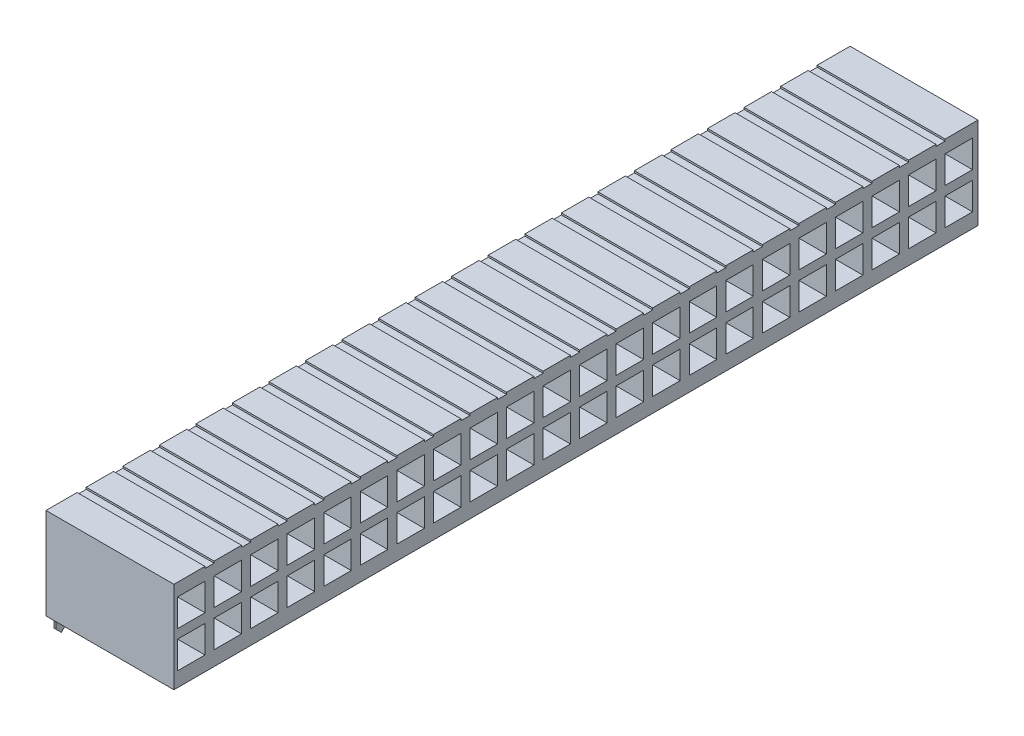
SolidWorks part; units mm, degrees
ref_plane "Alzado" through (0, 0, 0) normal (0, 0, 1) x (1, 0, 0)
ref_plane "Planta" through (0, 0, 0) normal (0, 1, 0) x (1, 0, 0)
ref_plane "Vista lateral" through (0, 0, 0) normal (1, 0, 0) x (0, 0, -1)
sketch "Croquis1" plane through (0, 0, 0) normal (1, 0, 0) x (0, 0, -1)
  line L1 (-22, 2.5) -> (22, 2.5)
  line L2 (-22, 2.5) -> (-22, -2.5)
  line L3 (-22, -2.5) -> (22, -2.5)
  line L4 (22, 2.5) -> (22, -2.5)
  line L5 (-22, 2.5) -> (22, -2.5) construction
  line L6 (-22, -2.5) -> (22, 2.5) construction
  point P0 (0, 0)
  dimension "D1" = 44
  dimension "D2" = 5
extrude "Extruir1" add sketch "Croquis1" along normal mid plane 7
sketch "Croquis2" plane through (3.5, 0, 0) normal (1, 0, 0) x (0, 0, -1)
  line L0 (22, 2.5) -> (-22, 2.5) construction
  line L1 (-21.8, 1.8) -> (-20.3, 1.8)
  line L2 (-21.8, 1.8) -> (-21.8, 0.3)
  line L3 (-21.8, 0.3) -> (-20.3, 0.3)
  line L4 (-20.3, 1.8) -> (-20.3, 0.3)
  line L5 (-21.8, 1.8) -> (-20.3, 0.3) construction
  line L6 (-21.8, 0.3) -> (-20.3, 1.8) construction
  line L7 (-22, 2.5) -> (-22, -2.5) construction
  point P0 (-21.05, 1.05)
  dimension "D1" = 1.5
  dimension "D2" = 1.5
  dimension "D3" = 0.7
  dimension "D4" = 0.2
extrude "Extruir2" cut sketch "Croquis2" against normal through all
pattern_linear "MatrizL1" count 22 spacing 2 along (0, 0, -1) count 2 spacing 2 along (0, -1, 0) of "Extruir2"
sketch "Croquis3" plane through (0, 0.3, 0) normal (0, 1, 0) x (1, 0, 0)
  line L2 (-3.6, -21.8) -> (0.1785, -21.8)
  line L3 (-3.6, -20.3) -> (0.1785, -20.3)
  line L4 (0.1785, -20.3) -> (0.1785, -21.8)
  line L5 (-3.5, 22) -> (-3.5, -22) construction
  line L6 (-3.6, -20.3) -> (-3.6, -21.8)
  line L7 (3.5, -21.8) -> (3.5, -20.3) construction
  line L8 (-3.5, -20.3) -> (3.5, -20.3) construction
  dimension "D1" = 0.1
  dimension "D2" = 3.3215
  dimension "D3" = 1.5
extrude "Extruir3" add sketch "Croquis3" along normal blind 0.1
sketch "Croquis5" plane through (-3.6, 0, 0) normal (-1, 0, 0) x (0, 0, 1)
  line L0 (20.3, 0.4) -> (20.3, -1.7)
  line L1 (22, -2.5) -> (-22, -2.5) construction
  line L2 (20.3, 0.4) -> (21.8, 0.4)
  line L3 (21.8, 0.4) -> (21.8, -1.7)
  line L4 (21.8, -1.7) -> (20.3, -1.7) construction
  line L5 (20.3, -1.7) -> (20.76, -2.5)
  line L6 (21.8, -0.2) -> (21.8, -1.7) construction
  line L7 (21.8, -1.7) -> (21.3581, -2.5)
  line L8 (21.3581, -2.5) -> (21.3581, -3.5031)
  line L9 (21.3581, -3.5031) -> (21.0591, -3.8022)
  line L10 (21.0591, -3.8022) -> (20.76, -3.5031)
  line L11 (20.76, -3.5031) -> (20.76, -2.5)
  line L12 (20.3, 0.3) -> (21.8, 0.3) construction
  dimension "D1" = 0.4419
  dimension "D2" = 0.7409
  dimension "D3" = 0.1
  dimension "D4" = 1.5
  dimension "D5" = 3.8031
extrude "Extruir9" add sketch "Croquis5" along normal blind 0.1
sketch "Croquis8" plane through (-3.6, 0, 0) normal (1, 0, 0) x (0, 0, -1)
  line L0 (-20.3, 0.3) -> (-20.3, -1.7) construction
  line L1 (-21.8, -1.7) -> (-20.3, -1.7)
  line L2 (-21.8, -1.7) -> (-21.8, -1.6)
  line L3 (-21.8, -1.6) -> (-20.3, -1.6)
  line L4 (-20.3, -1.7) -> (-20.3, -1.6)
  dimension "D1" = 0.1
extrude "Extruir11" add sketch "Croquis8" along normal up to surface (3.7785 mm away) up to face at (0.1785, 0.35, 21.05)
fillet "Redondeo1" radius 0.1 1 edges at (-3.7, 0.4, 21.05)
pattern_linear "MatrizL3" count 22 spacing 2 along (0, 0, -1) of "Extruir9", "Redondeo1", "Extruir3", "Extruir11"
sketch "Croquis6" plane through (3.5, 0, 0) normal (1, 0, 0) x (0, 0, -1)
  line L0 (22, 2.5) -> (-22, 2.5) construction
  line L1 (-20.3, 2.5) -> (-19.8, 2.5)
  line L2 (-20.3, 2.5) -> (-20.3, 2.4)
  line L3 (-20.3, 2.4) -> (-19.8, 2.4)
  line L4 (-19.8, 2.5) -> (-19.8, 2.4)
  dimension "D1" = 0.5
  dimension "D2" = 0.1
extrude "Extruir10" cut sketch "Croquis6" against normal through all
pattern_linear "MatrizL4" count 21 spacing 2 along (0, 0, -1) of "Extruir10"
